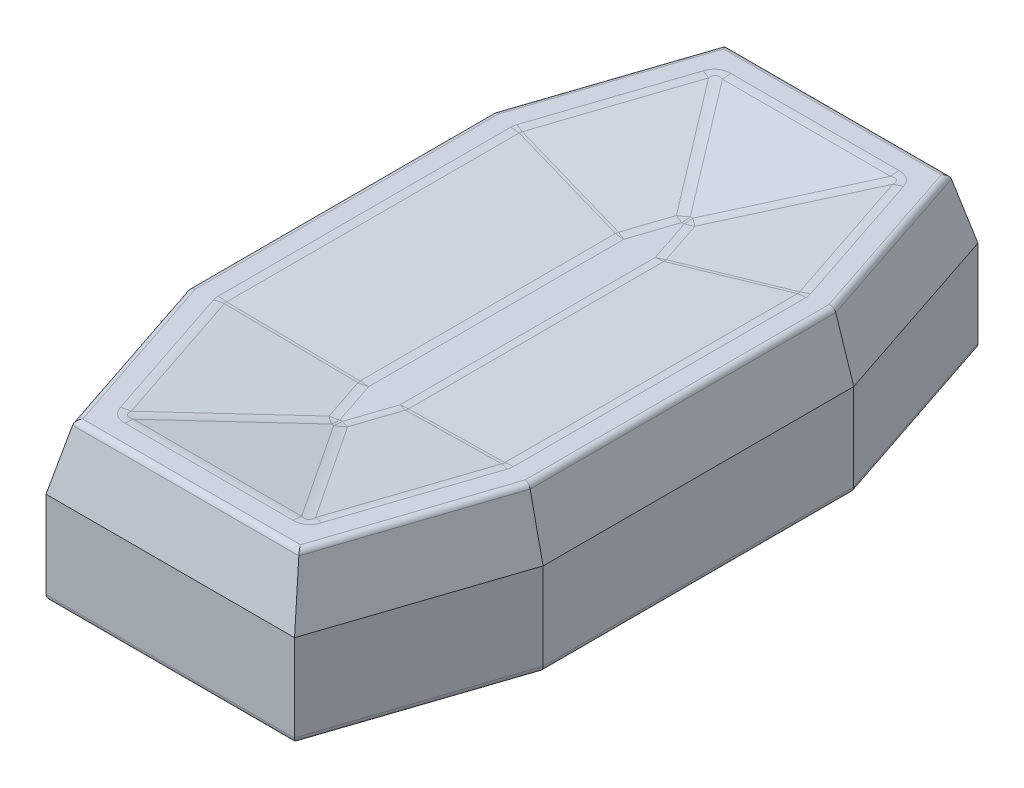
SolidWorks part; units mm, degrees
ref_plane "Front Plane" through (0, 0, 0) normal (0, 0, 1) x (1, 0, 0)
ref_plane "Top Plane" through (0, 0, 0) normal (0, 1, 0) x (1, 0, 0)
ref_plane "Right Plane" through (0, 0, 0) normal (1, 0, 0) x (0, 0, -1)
sketch "Sketch1" plane through (0, 0, 0) normal (0, 1, 0) x (1, 0, 0)
  line L0 (-7.62, 6.35) -> (-5.08, 13.97)
  line L1 (-5.08, 13.97) -> (5.08, 13.97)
  line L2 (-7.62, 6.35) -> (-7.62, -6.35)
  line L3 (-5.08, -13.97) -> (5.08, -13.97)
  line L4 (7.62, 6.35) -> (7.62, -6.35)
  line L5 (-7.62, 13.97) -> (7.62, -13.97) construction
  line L6 (-7.62, -13.97) -> (7.62, 13.97) construction
  line L7 (5.08, 13.97) -> (7.62, 6.35)
  line L8 (5.08, -13.97) -> (7.62, -6.35)
  line L9 (-7.62, -6.35) -> (-5.08, -13.97)
  point P0 (0, 0)
  dimension "D1" = 15.24
  dimension "D2" = 27.94
  dimension "D3" = 2.54
  dimension "D4" = 7.62
  dimension "D5" = 2.54
  dimension "D6" = 7.62
  dimension "D7" = 2.54
  dimension "D8" = 7.62
  dimension "D9" = 7.62
  dimension "D10" = 2.54
extrude "Boss-Extrude1" add sketch "Sketch1" along normal blind 2.54 draft 15
sketch "Stem" plane through (0, 0, 0) normal (0, -1, 0) x (1, 0, 0)
  line L1 (-0.5625, 2.075) -> (0.5625, 2.075)
  line L2 (-0.5625, 2.075) -> (-0.5625, -2.075)
  line L3 (-0.5625, -2.075) -> (0.5625, -2.075)
  line L4 (0.5625, 2.075) -> (0.5625, -2.075)
  line L5 (-0.5625, 2.075) -> (0.5625, -2.075) construction
  line L6 (-0.5625, -2.075) -> (0.5625, 2.075) construction
  line L7 (2.0625, 0.6625) -> (-2.0625, 0.6625)
  line L8 (2.0625, 0.6625) -> (2.0625, -0.6625)
  line L9 (2.0625, -0.6625) -> (-2.0625, -0.6625)
  line L10 (-2.0625, 0.6625) -> (-2.0625, -0.6625)
  line L11 (2.0625, 0.6625) -> (-2.0625, -0.6625) construction
  line L12 (2.0625, -0.6625) -> (-2.0625, 0.6625) construction
  line L13 (-2.5, 2.5) -> (2.5, 2.5)
  line L14 (-3, 2) -> (-3, -2)
  line L15 (-2.5, -2.5) -> (2.5, -2.5)
  line L16 (3, 2) -> (3, -2)
  line L17 (-3, 2.5) -> (3, -2.5) construction
  line L18 (-3, -2.5) -> (3, 2.5) construction
  arc A0 (-3, -2) -> (-2.5, -2.5) centre (-2.5, -2) ccw
  arc A1 (-2.5, 2.5) -> (-3, 2) centre (-2.5, 2) ccw
  arc A2 (2.5, -2.5) -> (3, -2) centre (2.5, -2) ccw
  arc A3 (2.5, 2.5) -> (3, 2) centre (2.5, 2) cw
  point P0 (0, 0)
  point P6 (0, 0)
  point P11 (0, 0)
  dimension "D7" = 0.5
  dimension "D1" = 4.15
  dimension "D2" = 1.125
  dimension "D3" = 1.325
  dimension "D4" = 4.125
  dimension "D5" = 5
  dimension "D6" = 6
extrude "Boss-Extrude2" add sketch "Stem" along normal blind 3.8 contours A3 L13 A1 L14 A0 L15 A2 L16 L10 L7 L2 L1 L4 L8 L9 L3 region at (0, 0, 2.4219)
fillet "Fillet2" radius 0.1 8 edges at (-2.8536, -3.8, -2.3536) (-3, -3.8, 0) (-2.8536, -3.8, 2.3536) (0, -3.8, 2.5) (2.8536, -3.8, 2.3536) (3, -3.8, 0) (2.8536, -3.8, -2.3536) (0, -3.8, -2.5)
chamfer "Chamfer1" distance 0.2 angle 45 11 edges at (-0.5625, -3.8, -1.3688) (-1.3125, -3.8, -0.6625) (-2.0625, -3.8, 0) (0.5625, -3.8, -1.3688) (1.3125, -3.8, -0.6625) (2.0625, -3.8, 0) (1.3125, -3.8, 0.6625) (0.5625, -3.8, 1.3687) (0, -3.8, 2.075) (-0.5625, -3.8, 1.3687) (-1.3125, -3.8, 0.6625)
sketch "Sketch3" plane through (0, 0, 0) normal (0, -1, 0) x (1, 0, 0)
  line L0 (-7.62, 6.35) -> (-7.62, -6.35)
  line L1 (-7.62, -6.35) -> (-5.08, -13.97)
  line L2 (-5.08, -13.97) -> (5.08, -13.97)
  line L3 (5.08, -13.97) -> (7.62, -6.35)
  line L4 (7.62, -6.35) -> (7.62, 6.35)
  line L5 (7.62, 6.35) -> (5.08, 13.97)
  line L6 (5.08, 13.97) -> (-5.08, 13.97)
  line L7 (-5.08, 13.97) -> (-7.62, 6.35)
  line L44 (-6.35, -6.1439) -> (-4.1646, -12.7)
  line L45 (-4.1646, -12.7) -> (4.1646, -12.7)
  line L46 (4.1646, -12.7) -> (6.35, -6.1439)
  line L47 (6.35, -6.1439) -> (6.35, 6.1439)
  line L48 (6.35, 6.1439) -> (4.1646, 12.7)
  line L49 (4.1646, 12.7) -> (-4.1646, 12.7)
  line L50 (-4.1646, 12.7) -> (-6.35, 6.1439)
  line L51 (-6.35, 6.1439) -> (-6.35, -6.1439)
  line L52 (-6.35, -6.1439) -> (-4.1646, -12.7)
  line L53 (-4.1646, -12.7) -> (4.1646, -12.7)
  line L54 (4.1646, -12.7) -> (6.35, -6.1439)
  line L55 (6.35, -6.1439) -> (6.35, 6.1439)
  line L56 (6.35, 6.1439) -> (4.1646, 12.7)
  line L57 (4.1646, 12.7) -> (-4.1646, 12.7)
  line L58 (-4.1646, 12.7) -> (-6.35, 6.1439)
  line L59 (-6.35, 6.1439) -> (-6.35, -6.1439)
  dimension "D1" = 1.27
extrude "Boss-Extrude3" add sketch "Sketch3" along normal blind 3.8
fillet "Fillet3" radius 0.25 16 edges at (0, -3.8, -12.7) (5.2573, -3.8, -9.422) (6.35, -3.8, 0) (5.2573, -3.8, 9.422) (0, -3.8, 12.7) (-5.2573, -3.8, 9.422) (-6.35, -3.8, 0) (-5.2573, -3.8, -9.422) (0, -3.8, 13.97) (6.35, -3.8, 10.16) (7.62, -3.8, 0) (6.35, -3.8, -10.16) (0, -3.8, -13.97) (-6.35, -3.8, -10.16) (-7.62, -3.8, 0) (-6.35, -3.8, 10.16)
fillet "Fillet5" radius 0.5 16 edges at (0, 0, 2.5) (-2.8536, 0, 2.3536) (-3, 0, 0) (-2.8536, 0, -2.3536) (0, 0, -2.5) (2.8536, 0, -2.3536) (3, 0, 0) (2.8536, 0, 2.3536) (-5.2573, 0, 9.422) (0, 0, 12.7) (5.2573, 0, 9.422) (6.35, 0, 0) (5.2573, 0, -9.422) (0, 0, -12.7) (-5.2573, 0, -9.422) (-6.35, 0, 0)
fillet "Fillet6" radius 0.1 12 edges at (-1.3125, 0, 0.6625) (-0.5625, 0, 1.3687) (0, 0, 2.075) (0.5625, 0, 1.3687) (1.3125, 0, 0.6625) (2.0625, 0, 0) (1.3125, 0, -0.6625) (0.5625, 0, -1.3688) (0, 0, -2.075) (-0.5625, 0, -1.3688) (-1.3125, 0, -0.6625) (-2.0625, 0, 0)
fillet "Fillet7" radius 0.25 8 edges at (5.7644, 2.54, -9.7645) (6.9394, 2.54, 0) (5.7644, 2.54, 9.7645) (0, 2.54, 13.2894) (-5.7644, 2.54, 9.7645) (-6.9394, 2.54, 0) (-5.7644, 2.54, -9.7645) (0, 2.54, -13.2894)
sketch "Sketch5" plane through (0, 2.54, 0) normal (0, 1, 0) x (1, 0, 0)
  line L16 (5.8586, -6.0642) -> (5.8586, 6.0642)
  line L17 (5.8586, 6.0642) -> (3.8104, 12.2086)
  line L18 (3.8104, 12.2086) -> (-3.8104, 12.2086)
  line L19 (-3.8104, 12.2086) -> (-5.8586, 6.0642)
  line L20 (-5.8586, 6.0642) -> (-5.8586, -6.0642)
  line L21 (-5.8586, -6.0642) -> (-3.8104, -12.2086)
  line L22 (-3.8104, -12.2086) -> (3.8104, -12.2086)
  line L23 (3.8104, -12.2086) -> (5.8586, -6.0642)
  line L24 (5.8586, -6.0642) -> (5.8586, 6.0642)
  line L25 (5.8586, 6.0642) -> (3.8104, 12.2086)
  line L26 (3.8104, 12.2086) -> (-3.8104, 12.2086)
  line L27 (-3.8104, 12.2086) -> (-5.8586, 6.0642)
  line L28 (-5.8586, 6.0642) -> (-5.8586, -6.0642)
  line L29 (-5.8586, -6.0642) -> (-3.8104, -12.2086)
  line L30 (-3.8104, -12.2086) -> (3.8104, -12.2086)
  line L31 (3.8104, -12.2086) -> (5.8586, -6.0642)
  dimension "D1" = 0.889
extrude "Cut-Extrude1" cut sketch "Sketch5" against normal blind 0.889 draft 80
fillet "Fillet9" radius 2 24 edges at (0.4967, 1.651, 6.2064) (4.8345, 2.54, 9.1364) (0, 1.651, 7.1668) (1.9935, 2.0955, 9.6877) (0, 2.54, 12.2086) (-0.4967, 1.651, 6.2064) (-1.9935, 2.0955, 9.6877) (-4.8345, 2.54, 9.1364) (-0.8168, 1.651, 0) (-3.3377, 2.0955, 5.6551) (-5.8586, 2.54, 0) (-0.4967, 1.651, -6.2064) (-3.3377, 2.0955, -5.6551) (-4.8345, 2.54, -9.1364) (0, 1.651, -7.1668) (-1.9935, 2.0955, -9.6877) (0, 2.54, -12.2086) (0.4967, 1.651, -6.2064) (1.9935, 2.0955, -9.6877) (4.8345, 2.54, -9.1364) (3.3377, 2.0955, 5.6551) (0.8168, 1.651, 0) (3.3377, 2.0955, -5.6551) (5.8586, 2.54, 0)
